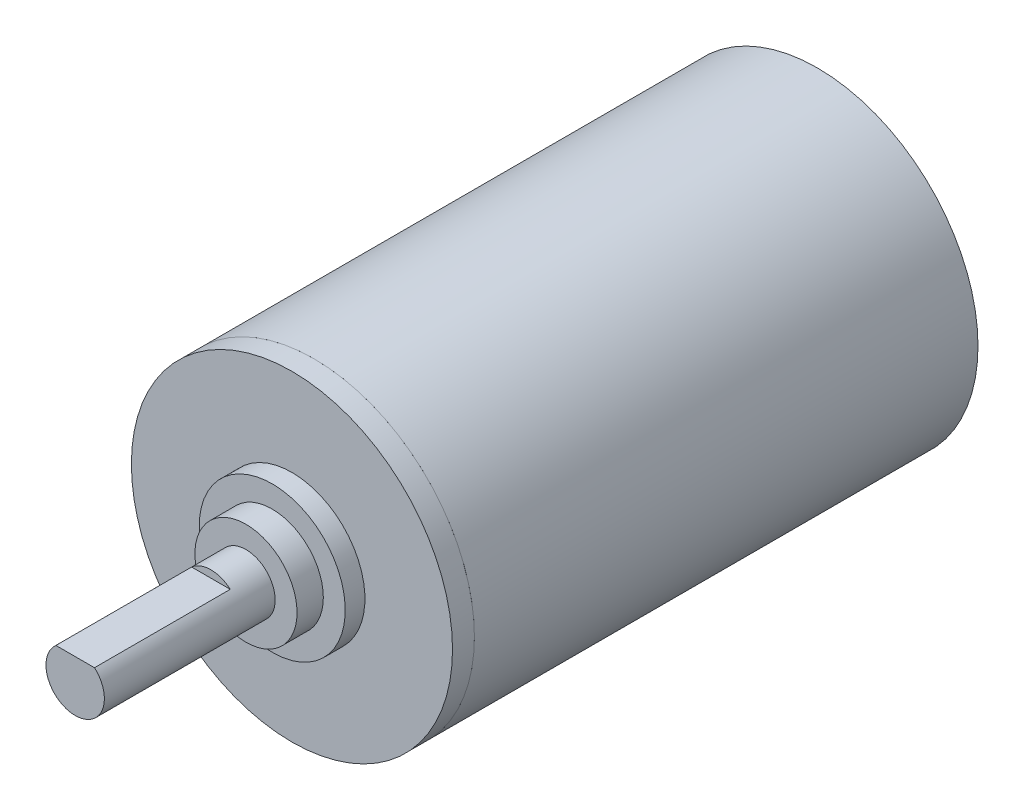
SolidWorks part; units mm, degrees
material "Alloy Steel"
ref_plane "Front Plane" through (0, 0, 0) normal (0, 0, 1) x (1, 0, 0)
ref_plane "Top Plane" through (0, 0, 0) normal (0, 1, 0) x (1, 0, 0)
ref_plane "Right Plane" through (0, 0, 0) normal (1, 0, 0) x (0, 0, -1)
sketch "Sketch1" plane through (0, 0, 0) normal (0, 0, 1) x (1, 0, 0)
  circle A0 centre (0, 0) radius 11
  circle A1 centre (0, 0) radius 5
  circle A2 centre (0, 0) radius 3.5
  circle A3 centre (0, 0) radius 2
  dimension "D1" = 22
  dimension "D2" = 10
  dimension "D3" = 7
  dimension "D4" = 4
extrude "Body" add sketch "Sketch1" against normal blind 36 contours A0 A1 | A1 A2 | A2 A3 | A3 region at (-10.6889, 0, 0) region at (-4.8586, 0, 0) region at (-3.401, 0, 0) region at (0, 0, 0)
extrude "Collar 1" add sketch "Sketch1<3>" along normal blind 1.35 contours A1 A2 region at (-4.8586, 0, 0)
sketch "Sketch1<3>" plane through (0, 0, 0) normal (0, 0, 1) x (1, 0, 0) same geometry as "Sketch1"
extrude "Collar 2" add sketch "Sketch1<4>" along normal blind 3.15 contours A2 A3 region at (-3.401, 0, 0)
sketch "Sketch1<4>" plane through (0, 0, 0) normal (0, 0, 1) x (1, 0, 0) same geometry as "Sketch1"
sketch "Sketch4" plane through (0, 0, 0) normal (0, 0, 1) x (1, 0, 0)
  circle A0 centre (0, 0) radius 11
  circle A1 centre (0, 0) radius 11 construction
  circle A2 centre (0, 0) radius 10.5
  dimension "D1" = 0.5
extrude "Cap Ring" cut sketch "Sketch4" against normal blind 0.001 from offset 1.5 offset against normal yes
extrude "Shaft" add sketch "Sketch1<5>" along normal blind 14.85 contours A3 region at (0, 0, 0)
sketch "Sketch1<5>" plane through (0, 0, 0) normal (0, 0, 1) x (1, 0, 0) same geometry as "Sketch1"
sketch "Sketch3" plane through (0, 0, 14.85) normal (0, 0, 1) x (1, 0, 0)
  line L0 (0, -2) -> (0, 1.5)
  line L1 (0, 1.5) -> (-1.3229, 1.5)
  line L2 (0, 1.5) -> (1.3229, 1.5)
  circle A0 centre (0, 0) radius 2 construction
  circle A1 centre (0, 0) radius 2 construction
  circle A2 centre (0, 0) radius 2
  circle M1 centre (0, 0) radius 2
extrude "Key Way" cut sketch "Sketch3" against normal blind 9.3 contours L1 L2 M1 region at (0, 1.7023, 14.85)
sketch "Sketch2" plane through (0, 0, -36) normal (0, 0, -1) x (-1, 0, 0)
  circle A0 centre (0, 0) radius 1.5
  circle A1 centre (0, 0) radius 5
extrude "Recess for Motor Collar" cut sketch "Sketch2" against normal blind 1
extrude "Recess for Motor Shaft" cut sketch "Sketch2<2>" against normal blind 10.3 contours A0 region at (0, 0, -36)
sketch "Sketch2<2>" plane through (0, 0, -36) normal (0, 0, -1) x (-1, 0, 0) same geometry as "Sketch2"
